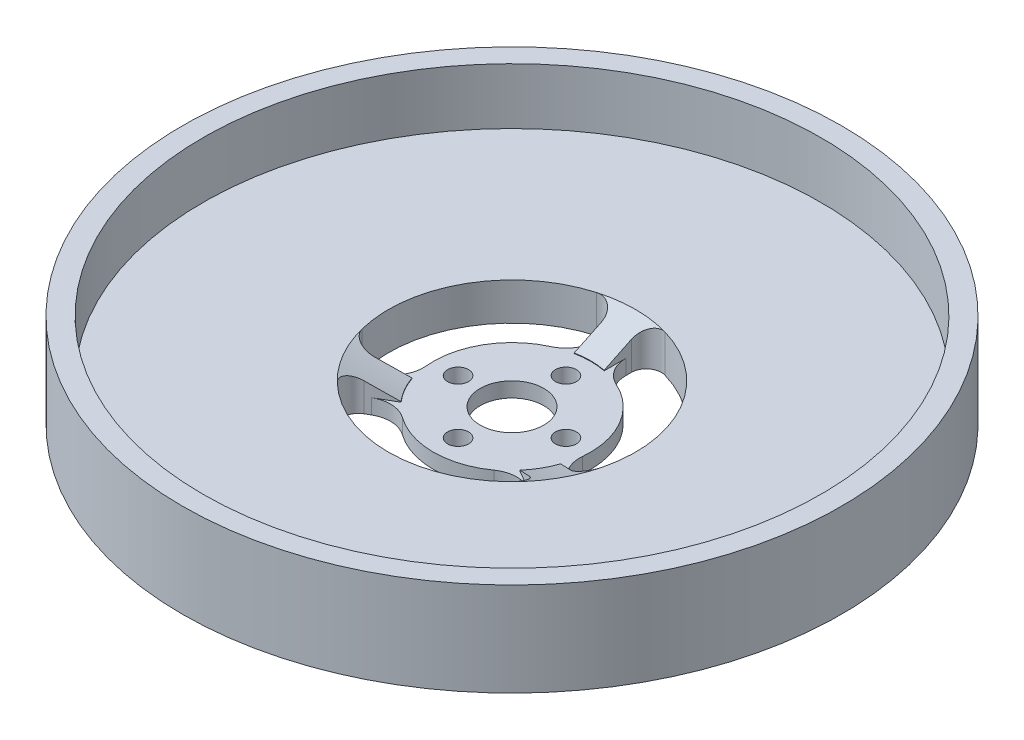
SolidWorks part; units mm, degrees
ref_plane "Front Plane" through (0, 0, 0) normal (0, 0, 1) x (1, 0, 0)
ref_plane "Top Plane" through (0, 0, 0) normal (0, 1, 0) x (1, 0, 0)
ref_plane "Right Plane" through (0, 0, 0) normal (1, 0, 0) x (0, 0, -1)
sketch "Sketch2" plane through (0, 0, 0) normal (0, 1, 0) x (1, 0, 0)
  circle A0 centre (0, 0) radius 44
extrude "Boss-Extrude2" add sketch "Sketch2" along normal blind 12.5
sketch "Sketch5" plane through (0, 12.5, 0) normal (0, 1, 0) x (1, 0, 0)
  circle A0 centre (0, 0) radius 41.25
  dimension "D1" = 82.5
extrude "Cut-Extrude2" cut sketch "Sketch5" against normal blind 7.5
sketch "Sketch6" plane through (0, 5, 0) normal (0, 1, 0) x (1, 0, 0)
  circle A0 centre (0, 0) radius 10.5
extrude "Cut-Extrude3" cut sketch "Sketch6" against normal blind 3
sketch "Sketch7" plane through (0, 2, 0) normal (0, 1, 0) x (1, 0, 0)
  circle A0 centre (0, 0) radius 4.25
  dimension "D1" = 8.5
extrude "Cut-Extrude4" cut sketch "Sketch7" against normal through all
sketch "Sketch8" plane through (0, 2, 0) normal (0, 1, 0) x (1, 0, 0)
  line L0 (-32.1696, 7.2) -> (36.5413, 7.2) construction
  circle A0 centre (0, 7.2) radius 1.4
  dimension "D1" = 7.2
extrude "Cut-Extrude5" cut sketch "Sketch8" against normal through all
pattern_circular "CirPattern2" count 4 over 360 about axis through (0, 2, 0) along (0, 1, 0) of "Cut-Extrude5"
sketch "Sketch11" plane through (0, 0, 0) normal (0, -1, 0) x (1, 0, 0)
  line L0 (0, 0) -> (0, -24.4942) construction
  line L1 (0, 0) -> (40.7412, 23.522) construction
  line L2 (-2, -10.3078) -> (-2, -16.3783)
  line L3 (0, 0) -> (-45.2396, 26.1191) construction
  line L4 (2, -10.3078) -> (2, -16.3783)
  line L5 (15.1841, 6.4571) -> (9.9268, 3.4218)
  line L6 (13.1841, 9.9212) -> (7.9268, 6.8859)
  line L7 (-7.9268, 6.8859) -> (-13.1841, 9.9212)
  line L8 (-15.1841, 6.4571) -> (-9.9268, 3.4218)
  circle A0 centre (0, 0) radius 10.5
  circle A1 centre (0, 0) radius 16.5
  dimension "D1" = 6
  dimension "D2" = 21
  dimension "D3" = 2
  dimension "D4" = 4
  dimension "D5" = 120
  dimension "D6" = 120
  dimension "D7" = 2
  dimension "D8" = 2
  dimension "D9" = 2
  dimension "D10" = 2
extrude "Cut-Extrude6" cut sketch "Sketch11" against normal blind 9 contours L6 A1 L7 A0 | L8 A1 L2 A0 | L4 A1 L5 A0 region at (-10.3663, 0, -5.985) region at (10.3663, 0, -5.985) region at (0, 0, 11.97)
chamfer "Chamfer1" distance 6 angle 26 3 edges at (-9.0933, 5, 5.25) (0, 5, -10.5) (9.0933, 5, 5.25) first distance on face at (0, 5, 41.25)
fillet "Fillet2" radius 4 6 edges at (7.9268, 1, 6.8859) (9.9268, 1, 3.4218) (2, 1, -10.3078) (-2, 1, -10.3078) (-9.9268, 1, 3.4218) (-7.9268, 1, 6.8859)
fillet "Fillet3" radius 2 6 edges at (15.1841, 2.5, 6.4571) (13.1841, 2.5, 9.9212) (-15.1841, 2.5, 6.4571) (-13.1841, 2.5, 9.9212) (2, 2.5, -16.3783) (-2, 2.5, -16.3783)
